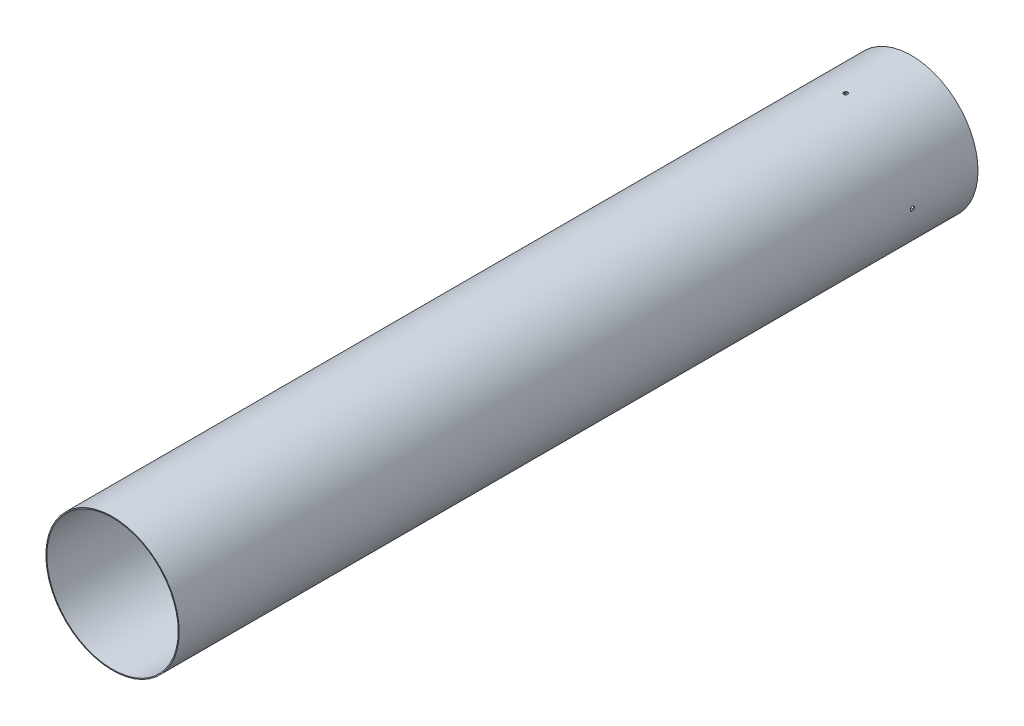
SolidWorks part; units mm, degrees
ref_plane "Front Plane" through (0, 0, 0) normal (0, 0, 1) x (1, 0, 0)
ref_plane "Top Plane" through (0, 0, 0) normal (0, 1, 0) x (1, 0, 0)
ref_plane "Right Plane" through (0, 0, 0) normal (1, 0, 0) x (0, 0, -1)
sketch "Sketch1" plane through (0, 0, 0) normal (0, 0, 1) x (1, 0, 0)
  circle A0 centre (0, 0) radius 79.375
  circle A1 centre (0, 0) radius 80.518
  dimension "D1" = 158.75
  dimension "D2" = 1.143
extrude "Boss-Extrude1" add sketch "Sketch1" along normal blind 965.2
ref_plane "Plane1" through (0, 80.518, 0) normal (0, 1, 0) x (1, 0, 0)
sketch "Sketch2" plane through (0, 80.518, 0) normal (0, 1, 0) x (1, 0, 0)
  line L0 (79.375, 0) -> (-79.375, 0) construction
  point P0 (0, -79.375)
  dimension "D1" = 79.375
hole_wizard "#10 (0.1935) Diameter Hole1" positions "Sketch3" profile "Sketch4" hole size "#10" standard "ANSI Inch" end condition up to next
sketch "Sketch3" plane through (0, 80.518, 0) normal (0, 1, 0) x (1, 0, 0)
  point P0 (0, -79.375)
sketch "Sketch4" plane through (0, 80.518, 79.375) normal (1, 0, 0) x (0, 0, 1)
  line L0 (0, 0) -> (0, 1.143)
  line L1 (0, 1.143) -> (2.4574, 1.143)
  line L2 (2.4574, 1.143) -> (2.4574, 0)
  line L5 (2.4574, 0) -> (0, 0)
  line L11 (0, -6.35) -> (0, 107.95) construction
  dimension "Thru Hole Dia." = 4.9149
  dimension "Thru Hole Depth" = 1.143
pattern_circular "CirPattern1" count 4 over 360 about axis through (0, 0, 0) along (0, 0, 1) of "#10 (0.1935) Diameter Hole1"
